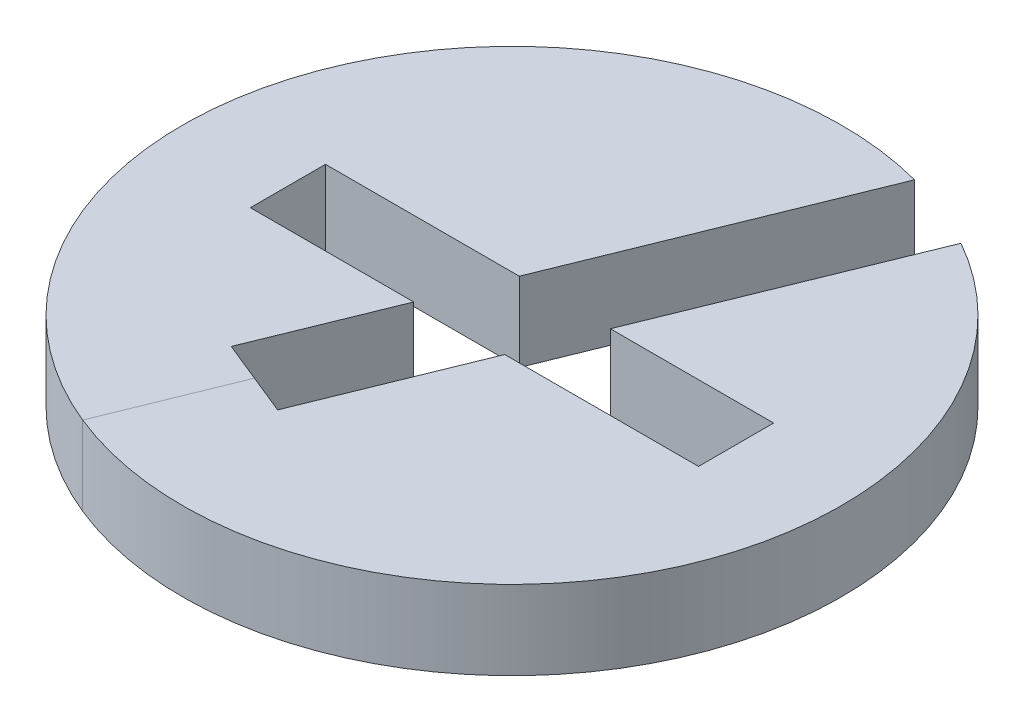
SolidWorks part; units mm, degrees
ref_plane "Front Plane" through (0, 0, 0) normal (0, 0, 1) x (1, 0, 0)
ref_plane "Top Plane" through (0, 0, 0) normal (0, 1, 0) x (1, 0, 0)
ref_plane "Right Plane" through (0, 0, 0) normal (1, 0, 0) x (0, 0, -1)
sketch "Sketch1" plane through (0, 0, 0) normal (0, 1, 0) x (1, 0, 0)
  line L0 (-12.5, 0) -> (12.5, 0) construction
  line L1 (-12.5, 0) -> (12.5, 0) construction
  circle A0 centre (0, 0) radius 12.5
extrude "Boss-Extrude1" add sketch "Sketch1" along normal blind 1.5 and the other way blind 1.5
sketch "Sketch2" plane through (0, -1.5, 0) normal (0, -1, 0) x (1, 0, 0)
  line L1 (-8.5, -1.425) -> (8.5, -1.425)
  line L2 (-8.5, -1.425) -> (-8.5, 1.425)
  line L3 (-8.5, 1.425) -> (8.5, 1.425)
  line L4 (8.5, -1.425) -> (8.5, 1.425)
  line L5 (0, 1.425) -> (0, -1.425) construction
  line L6 (-8.5, 0) -> (8.5, 0) construction
  point P0 (0, 0)
  dimension "D1" = 2.85
extrude "Cut-Extrude1" cut sketch "Sketch2" against normal through all
sketch "Sketch3" plane through (0, 0, 0) normal (0, -1, 0) x (1, 0, 0)
  line L0 (3.2204, -12.1836) -> (-4.3041, 6.347)
  line L1 (3.2204, -12.1836) -> (6.1852, -10.9796)
  line L2 (-4.3041, 6.347) -> (-1.3392, 7.5509)
  line L3 (6.1852, -10.9796) -> (-1.3392, 7.5509)
  line L4 (-2.8217, 6.949) -> (4.7028, -11.5816) construction
  line L5 (-0.5419, -2.9183) -> (2.423, -1.7144) construction
  line L6 (0, -1000) -> (0, 49000) construction
  circle A0 centre (0, 0) radius 12.5 construction
  point P0 (-4.7028, 11.5816)
  point P1 (0.9406, -2.3163)
  dimension "D1" = 3.2
  dimension "D2" = 22.1
  dimension "D3" = 5
extrude "Cut-Extrude2" cut sketch "Sketch3" against normal through all both and the other way through all
ref_axis "Axis1" through (-2.8217, 0, 6.949) along (0.3762, 0, -0.9265)
ref_plane "Plane1" through (0, 0, 0) normal (-0.9265, 0, -0.3762) x (-0.3762, 0, 0.9265)
split "Split2" trim tools "Plane1" bodies to split 103 resulting bodies 110 111
